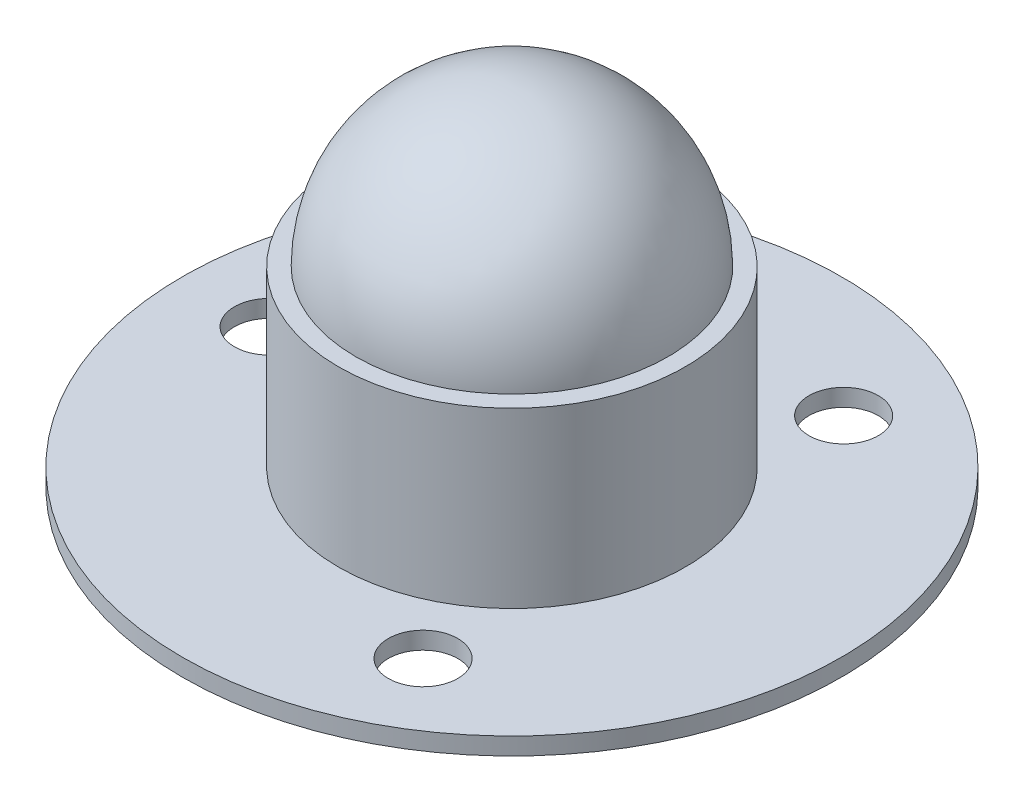
SolidWorks part; units mm, degrees
material "1023 Carbon Steel Sheet (SS)"
ref_plane "Front Plane" through (0, 0, 0) normal (0, 0, 1) x (1, 0, 0)
ref_plane "Top Plane" through (0, 0, 0) normal (0, 1, 0) x (1, 0, 0)
ref_plane "Right Plane" through (0, 0, 0) normal (1, 0, 0) x (0, 0, -1)
sketch "Sketch1" plane through (0, 0, 0) normal (0, 1, 0) x (1, 0, 0)
  line L0 (-19, 0) -> (-14, 0)
  circle A0 centre (0, 0) radius 19
  circle A1 centre (-14, 0) radius 2
  circle A2 centre (7, 12.1244) radius 2
  circle A3 centre (7, -12.1244) radius 2
  dimension "D1" = 3
extrude "Boss-Extrude1" add sketch "Sketch1" along normal mid plane 1 contours A1 A0 A3 A2 region at (0, 0, 0)
sketch "Sketch2" plane through (0, 0.5, 0) normal (0, 1, 0) x (1, 0, 0)
  circle A0 centre (0, 0) radius 10
extrude "Boss-Extrude2" add sketch "Sketch2" along normal blind 10
sketch "Sketch3" plane through (0, 10.5, 0) normal (0, 1, 0) x (1, 0, 0)
  line L0 (0, 9) -> (0, -9)
  circle A0 centre (0, 0) radius 9
revolve "Revolve1" add sketch "Sketch3" angle 360 about L0 region at (-3.8197, 10.5, 0)
